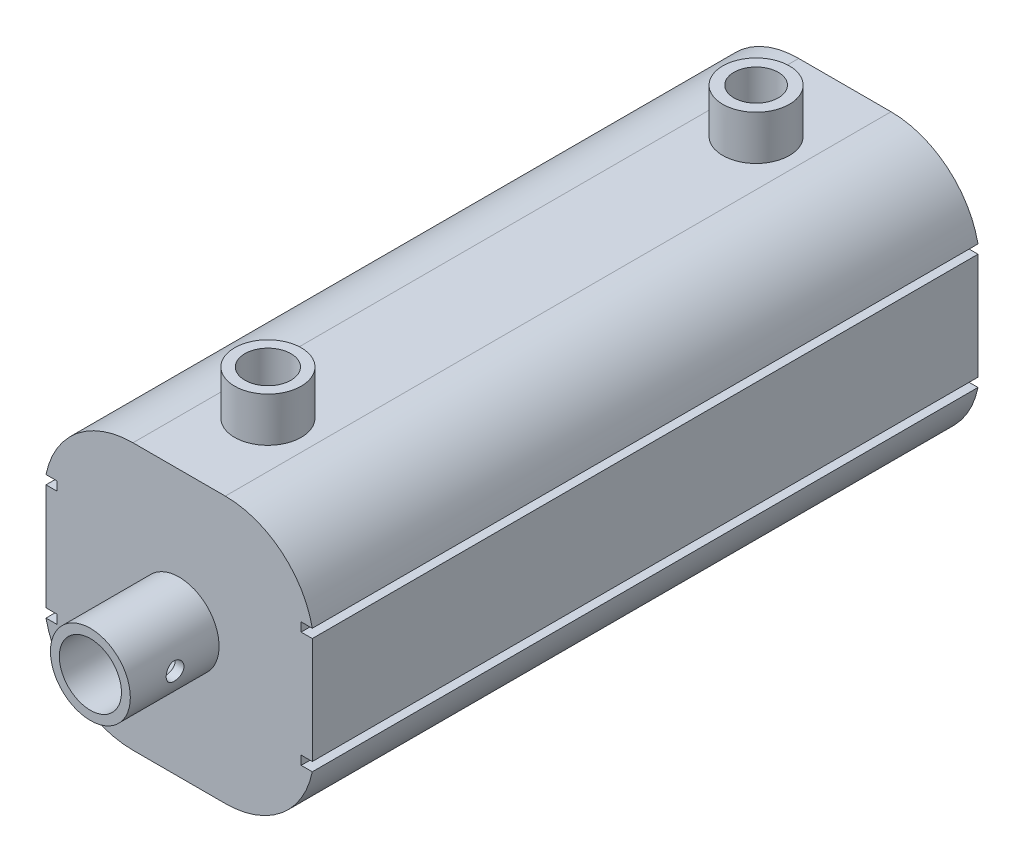
SolidWorks part; units mm, degrees
ref_plane "Front Plane" through (0, 0, 0) normal (0, 0, 1) x (1, 0, 0)
ref_plane "Top Plane" through (0, 0, 0) normal (0, 1, 0) x (1, 0, 0)
ref_plane "Right Plane" through (0, 0, 0) normal (1, 0, 0) x (0, 0, -1)
sketch "Sketch1" plane through (0, 0, 0) normal (1, 0, 0) x (0, 0, -1)
  line L1 (-37.5, -15) -> (37.5, -15)
  line L2 (-37.5, -15) -> (-37.5, 15)
  line L3 (-37.5, 15) -> (37.5, 15)
  line L4 (37.5, -15) -> (37.5, 15)
  line L5 (-37.5, -15) -> (37.5, 15) construction
  line L6 (-37.5, 15) -> (37.5, -15) construction
  point P0 (0, 0)
  dimension "D1" = 75
  dimension "D2" = 30
extrude "Boss-Extrude1" add sketch "Sketch1" along normal blind 30
sketch "Sketch3" plane through (0, 0, -37.5) normal (0, 0, -1) x (-1, 0, 0)
  line L0 (-30, -15) -> (-30, 15) construction
  circle A0 centre (-15, 0) radius 5
  point P2 (-30, 0)
  dimension "D2" = 10
  dimension "D1" = 15
extrude "Cut-Extrude1" cut sketch "Sketch3" against normal blind 60
sketch "Sketch4" plane through (0, 0, -37.5) normal (0, 0, -1) x (-1, 0, 0)
  line L0 (-30, -15) -> (-30, 15) construction
  line L1 (-30, 7) -> (-28.745, 7)
  line L2 (-30, 7) -> (-30, 6)
  line L3 (-30, 6) -> (-28.745, 6)
  line L4 (-28.745, 7) -> (-28.745, 6)
  line L5 (-30, 15) -> (0, 15) construction
  line L6 (-30, -6) -> (-28.745, -6)
  line L7 (-30, -6) -> (-30, -7)
  line L8 (-30, -7) -> (-28.745, -7)
  line L9 (-28.745, -6) -> (-28.745, -7)
  line L10 (-30, -15) -> (0, -15) construction
  line L11 (-15, 15) -> (-15, -15) construction
  line L12 (-1.255, -6) -> (-1.255, -7)
  line L13 (0, -7) -> (-1.255, -7)
  line L14 (0, -6) -> (-1.255, -6)
  line L15 (0, -6) -> (0, -7)
  line L16 (0, 7) -> (0, 6)
  line L17 (0, 6) -> (-1.255, 6)
  line L18 (-1.255, 7) -> (-1.255, 6)
  line L19 (0, 7) -> (-1.255, 7)
  dimension "D1" = 1
  dimension "D2" = 1
  dimension "D3" = 8
  dimension "D4" = 8
extrude "Cut-Extrude2" cut sketch "Sketch4" against normal through all
sketch "Sketch5" plane through (0, 15, 0) normal (0, 1, 0) x (1, 0, 0)
  line L0 (30, 37.5) -> (0, 37.5) construction
  circle A0 centre (15, 27.5) radius 2.5
  circle A1 centre (15, -27.5) radius 2.5971
  point P4 (15, 37.5)
  dimension "D1" = 55
  dimension "D2" = 10
extrude "Cut-Extrude3" cut sketch "Sketch5" against normal blind 20
sketch "Sketch6" plane through (0, 15, 0) normal (0, 1, 0) x (1, 0, 0)
  circle A0 centre (15, -27.5) radius 3.75
  circle A1 centre (15, 27.5) radius 3.75
  circle A2 centre (15, -27.5) radius 2.5971
  circle A3 centre (15, 27.5) radius 2.5
  dimension "D1" = 7.5
  dimension "D2" = 7.5
extrude "Boss-Extrude2" add sketch "Sketch6" along normal blind 5
sketch "Sketch7" plane through (0, 0, 22.5) normal (0, 0, -1) x (-1, 0, 0)
  circle A0 centre (-15, 0) radius 2.5
extrude "Cut-Extrude4" cut sketch "Sketch7" against normal blind 10
sketch "Sketch8" plane through (0, 0, 37.5) normal (0, 0, 1) x (1, 0, 0)
  line L0 (30, 6) -> (30, -6) construction
  line L1 (30, 15) -> (0, 15) construction
  circle A0 centre (15, 0) radius 3.5
  circle A1 centre (15, 0) radius 4.5
  dimension "D1" = 15
  dimension "D4" = 7
  dimension "D2" = 15
  dimension "D3" = 1
extrude "Boss-Extrude3" add sketch "Sketch8" along normal blind 10
sketch "Sketch9" plane through (0, 0, 0) normal (1, 0, 0) x (0, 0, -1)
  circle A0 centre (-42.4578, 0) radius 1
  dimension "D1" = 2
extrude "Cut-Extrude5" cut sketch "Sketch9" along normal through all
fillet "Fillet1" radius 10 4 edges at (30, -15, 0) (0, -15, 0) (0, 15, 0) (30, 15, 0)
